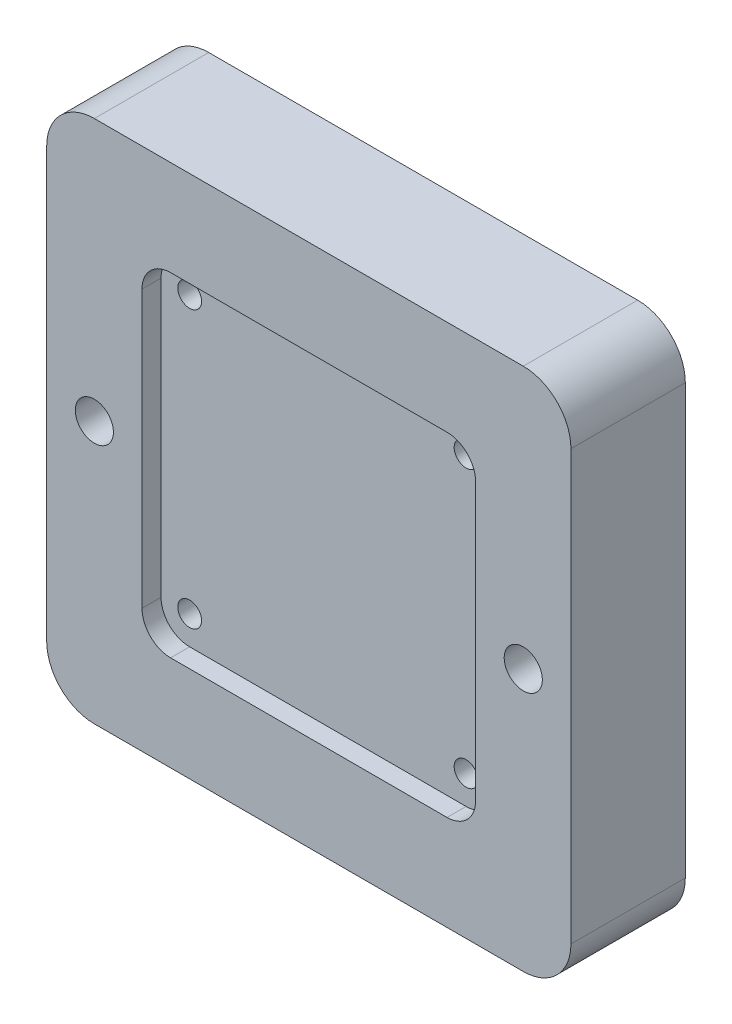
SolidWorks part; units mm, degrees
ref_plane "Front Plane" through (0, 0, 0) normal (0, 0, 1) x (1, 0, 0)
ref_plane "Top Plane" through (0, 0, 0) normal (0, 1, 0) x (1, 0, 0)
ref_plane "Right Plane" through (0, 0, 0) normal (1, 0, 0) x (0, 0, -1)
sketch "Sketch1" plane through (0, 0, 0) normal (0, 0, 1) x (1, 0, 0)
  line L0 (0, 55) -> (0, -55) construction
  line L1 (-45, 55) -> (45, 55)
  line L2 (-55, 45) -> (-55, -45)
  line L3 (-45, -55) -> (45, -55)
  line L4 (55, 45) -> (55, -45)
  line L5 (0, -55) -> (0, -35) construction
  line L6 (0, 35) -> (0, -35) construction
  line L7 (-29, 35) -> (29, 35)
  line L8 (-35, 29) -> (-35, -29)
  line L9 (-29, -35) -> (29, -35)
  line L10 (35, 29) -> (35, -29)
  line L11 (-35, 0) -> (-55, 0) construction
  line L12 (35, 0) -> (55, 0) construction
  arc A0 (45, 55) -> (55, 45) centre (45, 45) cw
  arc A1 (55, -45) -> (45, -55) centre (45, -45) cw
  arc A2 (-45, -55) -> (-55, -45) centre (-45, -45) cw
  arc A3 (-45, 55) -> (-55, 45) centre (-45, 45) ccw
  circle A4 centre (-45, 0) radius 4 construction
  circle A5 centre (45, 0) radius 4 construction
  arc A6 (-35, -29) -> (-29, -35) centre (-29, -29) ccw
  arc A7 (29, -35) -> (35, -29) centre (29, -29) ccw
  arc A8 (35, 29) -> (29, 35) centre (29, 29) ccw
  arc A9 (-29, 35) -> (-35, 29) centre (-29, 29) ccw
  point P31 (111.9206, -20.4692)
  point P32 (45, 0)
  point P39 (-45, 0)
  dimension "D1" = 10
  dimension "D2" = 8
  dimension "D3" = 6
  dimension "D4" = 70
  dimension "D5" = 70
  dimension "D6" = 20
extrude "Boss-Extrude1" add sketch "Sketch1" against normal blind 4
sketch "Sketch2" plane through (0, 0, -4) normal (0, 0, 1) x (1, 0, 0)
  line L8 (-45, -55) -> (45, -55) construction
  line L9 (55, 45) -> (55, -45) construction
  line L10 (-45, 55) -> (45, 55) construction
  line L11 (-55, 45) -> (-55, -45) construction
  line L12 (-45, -55) -> (45, -55)
  line L13 (55, 45) -> (55, -45)
  line L14 (-45, 55) -> (45, 55)
  line L15 (-55, 45) -> (-55, -45)
  arc A8 (45, -55) -> (55, -45) centre (45, -45) ccw construction
  arc A9 (55, 45) -> (45, 55) centre (45, 45) ccw construction
  arc A10 (-45, 55) -> (-55, 45) centre (-45, 45) ccw construction
  arc A11 (-55, -45) -> (-45, -55) centre (-45, -45) ccw construction
  arc A12 (45, -55) -> (55, -45) centre (45, -45) ccw
  arc A13 (55, 45) -> (45, 55) centre (45, 45) ccw
  arc A14 (-45, 55) -> (-55, 45) centre (-45, 45) ccw
  arc A15 (-55, -45) -> (-45, -55) centre (-45, -45) ccw
extrude "Boss-Extrude2" add sketch "Sketch2" against normal blind 20
sketch "Sketch3" plane through (0, 0, 0) normal (0, 0, 1) x (1, 0, 0)
  point P0 (-45, 0)
  point P3 (45, 0)
hole_wizard "Ø8.0mm Dowel Hole1" positions "Sketch3" profile "Sketch4" hole size "Ø8.0" standard "ANSI Metric"
sketch "Sketch4" plane through (-45, 0, 0) normal (1, 0, 0) x (0, -1, 0)
  line L0 (0, 0) -> (0, 20.4034)
  line L1 (0, 20.4034) -> (4, 18)
  line L2 (4, 18) -> (4, 0)
  line L5 (4, 0) -> (0, 0)
  line L10 (0, 20.4034) -> (-4, 18) construction
  line L11 (0, -6.35) -> (0, 107.95) construction
  dimension "Hole Dia." = 8
  dimension "Hole Depth" = 18
  dimension "Drill Angle" = 118
sketch "Sketch5" plane through (0, 0, -4) normal (0, 0, 1) x (1, 0, 0)
  line L0 (-29, 29) -> (29, -29) construction
  line L1 (-29, 29) -> (29, 29) construction
  line L2 (-29, 29) -> (-29, -29) construction
  line L3 (-29, -29) -> (29, -29) construction
  line L4 (29, 29) -> (29, -29) construction
  point P5 (-29, 29)
  point P7 (29, 29)
  point P8 (29, -29)
  point P9 (-29, -29)
  dimension "D1" = 58
sketch "Sketch6" plane through (0, 0, -4) normal (0, 0, 1) x (1, 0, 0)
  point P0 (-29, 29)
  point P3 (29, 29)
  point P6 (29, -29)
  point P9 (-29, -29)
hole_wizard "Tap Drill for M6x1.0 Tap1" positions "Sketch6" profile "Sketch7" hole size "M6x1.0" standard "ANSI Metric"
sketch "Sketch7" plane through (-29, 29, -4) normal (1, 0, 0) x (0, -1, 0)
  line L0 (0, 0) -> (0, 11.5022)
  line L1 (0, 11.5022) -> (2.5, 10)
  line L2 (2.5, 10) -> (2.5, 0)
  line L5 (2.5, 0) -> (0, 0)
  line L10 (0, 11.5022) -> (-2.5, 10) construction
  line L11 (0, -6.35) -> (0, 107.95) construction
  dimension "Hole Dia." = 5
  dimension "Hole Depth" = 10
  dimension "Drill Angle" = 118
